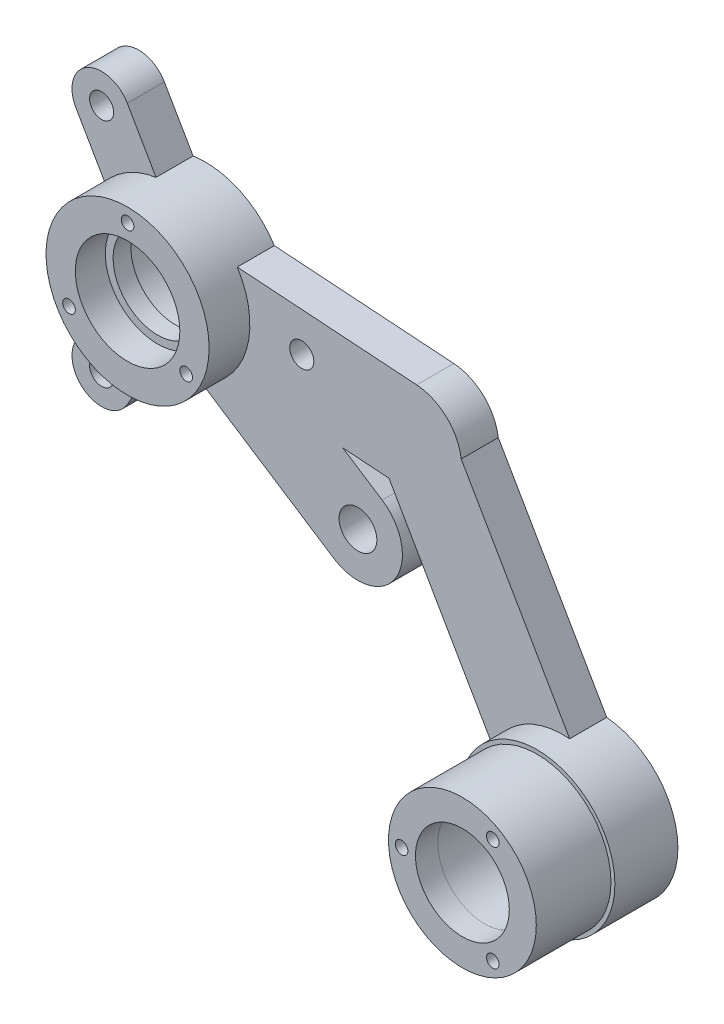
SolidWorks part; units mm, degrees
ref_plane "Front Plane" through (0, 0, 0) normal (0, 0, 1) x (1, 0, 0)
ref_plane "Top Plane" through (0, 0, 0) normal (0, 1, 0) x (1, 0, 0)
ref_plane "Right Plane" through (0, 0, 0) normal (1, 0, 0) x (0, 0, -1)
sketch "S01 - Bearing barrel" plane through (0, 0, 0) normal (0, 0, 1) x (1, 0, 0)
  circle A0 centre (0, 0) radius 22
  dimension "D1" = 44
extrude "01 - Bearing barrel" add sketch "S01 - Bearing barrel" along normal blind 21
sketch "S02 - Torque arm 1" plane through (0, 0, 0) normal (0, 0, 1) x (1, 0, 0)
  line L0 (0, 8) -> (36, 8)
  line L1 (36, -8) -> (0, -8)
  arc A0 (36, 8) -> (36, -8) centre (36, 0) cw
  arc A1 (0, -8) -> (0, 8) centre (0, 0) cw
  dimension "D1" = 8
  dimension "D2" = 36
extrude "02 - Torque arm 1" add sketch "S02 - Torque arm 1" along normal blind 10
sketch "S03 - Torque arm 2" plane through (0, 0, 0) normal (0, 0, 1) x (1, 0, 0)
  line L0 (-6.9282, -4) -> (-24.9282, 27.1769)
  line L1 (-11.0718, 35.1769) -> (6.9282, 4)
  arc A0 (-24.9282, 27.1769) -> (-11.0718, 35.1769) centre (-18, 31.1769) cw
  arc A1 (6.9282, 4) -> (-6.9282, -4) centre (0, 0) cw
  dimension "D1" = 8
  dimension "D2" = 8
  dimension "D3" = 6.9282
  dimension "D4" = 6.9282
  dimension "D5" = 11.0718
  dimension "D6" = 18
  dimension "D7" = 24.9282
  dimension "D8" = 27.1769
extrude "03 - Torque arm 2" add sketch "S03 - Torque arm 2" along normal blind 10
sketch "S04 - Torque arm 3" plane through (0, 0, 0) normal (0, 0, 1) x (1, 0, 0)
  line L0 (6.9282, -4) -> (-11.0718, -35.1769)
  line L1 (-24.9282, -27.1769) -> (-6.9282, 4)
  arc A0 (-11.0718, -35.1769) -> (-24.9282, -27.1769) centre (-18, -31.1769) cw
  arc A1 (-6.9282, 4) -> (6.9282, -4) centre (0, 0) cw
  dimension "D1" = 8
  dimension "D2" = 8
  dimension "D3" = 6.9282
  dimension "D4" = 6.9282
  dimension "D5" = 11.0718
  dimension "D6" = 18
  dimension "D7" = 24.9282
  dimension "D8" = 27.1769
extrude "04 - Torque arm 3" add sketch "S04 - Torque arm 3" along normal blind 10
sketch "S05 - Wheel arm root to rounded elbow" plane through (0, 0, 0) normal (0, 0, 1) x (1, 0, 0)
  line L0 (0.8909, 12.9694) -> (67.0223, 8.4265)
  line L1 (65.2405, -17.5124) -> (-0.8909, -12.9694)
  arc A0 (67.0223, 8.4265) -> (65.2405, -17.5124) centre (66.1314, -4.5429) cw
  arc A1 (-0.8909, -12.9694) -> (0.8909, 12.9694) centre (0, 0) cw
  dimension "D1" = 13
  dimension "D2" = 13
  dimension "D3" = 0.8909
  dimension "D4" = 65.2405
  dimension "D5" = 66.1314
  dimension "D6" = 67.0223
  dimension "D7" = 0.8909
  dimension "D8" = 8.4265
extrude "05 - Wheel arm root to rounded elbow" add sketch "S05 - Wheel arm root to rounded elbow" along normal blind 10
sketch "S06 - Long dropped wheel arm" plane through (0, 0, 0) normal (0, 0, 1) x (1, 0, 0)
  line L0 (76.5281, 1.4494) -> (116.8865, -68.5726)
  line L1 (96.093, -80.5573) -> (55.7347, -10.5353)
  arc A0 (116.8865, -68.5726) -> (96.093, -80.5573) centre (106.4898, -74.5649) cw
  arc A1 (55.7347, -10.5353) -> (76.5281, 1.4494) centre (66.1314, -4.5429) cw
  dimension "D1" = 12
  dimension "D2" = 12
  dimension "D3" = 55.7347
  dimension "D4" = 66.1314
  dimension "D5" = 76.5281
  dimension "D6" = 96.093
  dimension "D7" = 106.4898
  dimension "D8" = 116.8865
  dimension "D9" = 1.4494
  dimension "D10" = 68.5726
extrude "06 - Long dropped wheel arm" add sketch "S06 - Long dropped wheel arm" along normal blind 10
sketch "S07 - Broad cam follower mounting lug" plane through (0, 0, 0) normal (0, 0, 1) x (1, 0, 0)
  line L0 (6.5357, 10.064) -> (57.6946, -23.1589)
  line L1 (44.6232, -43.287) -> (-6.5357, -10.064)
  arc A0 (57.6946, -23.1589) -> (44.6232, -43.287) centre (51.1589, -33.223) cw
  arc A1 (-6.5357, -10.064) -> (6.5357, 10.064) centre (0, 0) cw
  dimension "D1" = 12
  dimension "D2" = 12
  dimension "D3" = 6.5357
  dimension "D4" = 44.6232
  dimension "D5" = 51.1589
  dimension "D6" = 57.6946
  dimension "D7" = 6.5357
  dimension "D8" = 23.1589
extrude "07 - Broad cam follower mounting lug" add sketch "S07 - Broad cam follower mounting lug" along normal blind 10
sketch "S08 - Bearing through relief" plane through (0, 0, 0) normal (0, 0, 1) x (1, 0, 0)
  circle A0 centre (0, 0) radius 12
  dimension "D1" = 24
extrude "08 - Bearing through relief" cut sketch "S08 - Bearing through relief" along normal blind 23 from offset 1 offset against normal yes
sketch "S09 - Inboard 6001 seat" plane through (0, 0, 0) normal (0, 0, 1) x (1, 0, 0)
  circle A0 centre (0, 0) radius 14.1
  dimension "D1" = 28.2
extrude "09 - Inboard 6001 seat" cut sketch "S09 - Inboard 6001 seat" along normal blind 8.2 from offset 0.1 offset against normal yes
sketch "S10 - Outboard 6001 seat" plane through (0, 0, 0) normal (0, 0, 1) x (1, 0, 0)
  circle A0 centre (0, 0) radius 14.1
  dimension "D1" = 28.2
extrude "10 - Outboard 6001 seat" cut sketch "S10 - Outboard 6001 seat" along normal blind 8.2 from offset 12.9
sketch "S11 - Keeper screws" plane through (0, 0, 0) normal (0, 0, 1) x (1, 0, 0)
  circle A0 centre (0, 18.25) radius 1.7
  circle A1 centre (-15.805, -9.125) radius 1.7
  circle A2 centre (15.805, -9.125) radius 1.7
  dimension "D1" = 3.4
  dimension "D2" = 3.4
  dimension "D3" = 3.4
  dimension "D4" = 15.805
  dimension "D5" = 15.805
  dimension "D6" = 18.25
  dimension "D7" = 9.125
extrude "11 - Keeper screws" cut sketch "S11 - Keeper screws" along normal blind 23 from offset 1 offset against normal yes
sketch "S12 - Torque pin retaining stems" plane through (0, 0, 0) normal (0, 0, 1) x (1, 0, 0)
  circle A0 centre (36, 0) radius 3.25
  circle A1 centre (-18, 31.1769) radius 3.25
  circle A2 centre (-18, -31.1769) radius 3.25
  dimension "D1" = 6.5
  dimension "D2" = 6.5
  dimension "D3" = 6.5
  dimension "D4" = 36
  dimension "D5" = 18
  dimension "D6" = 31.1769
  dimension "D7" = 31.1769
extrude "12 - Torque pin retaining stems" cut sketch "S12 - Torque pin retaining stems" along normal blind 12 from offset 1 offset against normal yes
sketch "S13 - Wheel tip through-bolt land" plane through (0, 0, 0) normal (0, 0, 1) x (1, 0, 0)
  circle A0 centre (106.4898, -74.5649) radius 21
  dimension "D1" = 42
  dimension "D2" = 106.4898
  dimension "D3" = 74.5649
extrude "13 - Wheel tip through-bolt land" add sketch "S13 - Wheel tip through-bolt land" along normal blind 10
sketch "S14 - Inboard 6808 inner-race shoulder" plane through (0, 0, 0) normal (0, 0, 1) x (1, 0, 0)
  circle A0 centre (106.4898, -74.5649) radius 21
  dimension "D1" = 42
  dimension "D2" = 106.4898
  dimension "D3" = 74.5649
extrude "14 - Inboard 6808 inner-race shoulder" add sketch "S14 - Inboard 6808 inner-race shoulder" along normal blind 7 from offset 10
sketch "S15 - Hollow 6808 wheel-bearing journal" plane through (0, 0, 0) normal (0, 0, 1) x (1, 0, 0)
  circle A0 centre (106.4898, -74.5649) radius 19.94
  dimension "D1" = 39.88
  dimension "D2" = 106.4898
  dimension "D3" = 74.5649
extrude "15 - Hollow 6808 wheel-bearing journal" add sketch "S15 - Hollow 6808 wheel-bearing journal" along normal blind 20.15 from offset 17
sketch "S16 - Axial motor installation passage" plane through (0, 0, 0) normal (0, 0, 1) x (1, 0, 0)
  circle A0 centre (106.4898, -74.5649) radius 12.66
  dimension "D1" = 25.32
  dimension "D2" = 106.4898
  dimension "D3" = 74.5649
extrude "16 - Axial motor installation passage" cut sketch "S16 - Axial motor installation passage" along normal blind 37.55 from offset 0.2 offset against normal yes
sketch "S17 - Gearbox body and wiring approach" plane through (0, 0, 0) normal (0, 0, 1) x (1, 0, 0)
  circle A0 centre (106.4898, -74.5649) radius 12.85
  dimension "D1" = 25.7
  dimension "D2" = 106.4898
  dimension "D3" = 74.5649
extrude "17 - Gearbox body and wiring approach" cut sketch "S17 - Gearbox body and wiring approach" along normal blind 31.35 from offset 0.2 offset against normal yes
sketch "S18 - Wheel faceplate through-bolt pattern" plane through (0, 0, 0) normal (0, 0, 1) x (1, 0, 0)
  circle A0 centre (114.6898, -60.3621) radius 1.7
  circle A1 centre (90.0898, -74.5649) radius 1.7
  circle A2 centre (114.6898, -88.7678) radius 1.7
  dimension "D1" = 3.4
  dimension "D2" = 3.4
  dimension "D3" = 3.4
  dimension "D4" = 90.0898
  dimension "D5" = 114.6898
  dimension "D6" = 60.3621
  dimension "D7" = 74.5649
  dimension "D8" = 88.7678
extrude "18 - Wheel faceplate through-bolt pattern" cut sketch "S18 - Wheel faceplate through-bolt pattern" along normal blind 37.55 from offset 0.2 offset against normal yes
sketch "S19 - Through bore for steel follower bush" plane through (0, 0, 0) normal (0, 0, 1) x (1, 0, 0)
  circle A0 centre (51.1589, -33.223) radius 5.1
  dimension "D1" = 10.2
  dimension "D2" = 51.1589
  dimension "D3" = 33.223
extrude "19 - Through bore for steel follower bush" cut sketch "S19 - Through bore for steel follower bush" along normal blind 12 from offset 1 offset against normal yes
sketch "S20 - Flush seat for bush flange" plane through (0, 0, 0) normal (0, 0, 1) x (1, 0, 0)
  circle A0 centre (51.1589, -33.223) radius 7.6
  dimension "D1" = 15.2
  dimension "D2" = 51.1589
  dimension "D3" = 33.223
extrude "20 - Flush seat for bush flange" cut sketch "S20 - Flush seat for bush flange" along normal blind 2.1 from offset 0.1 offset against normal yes
